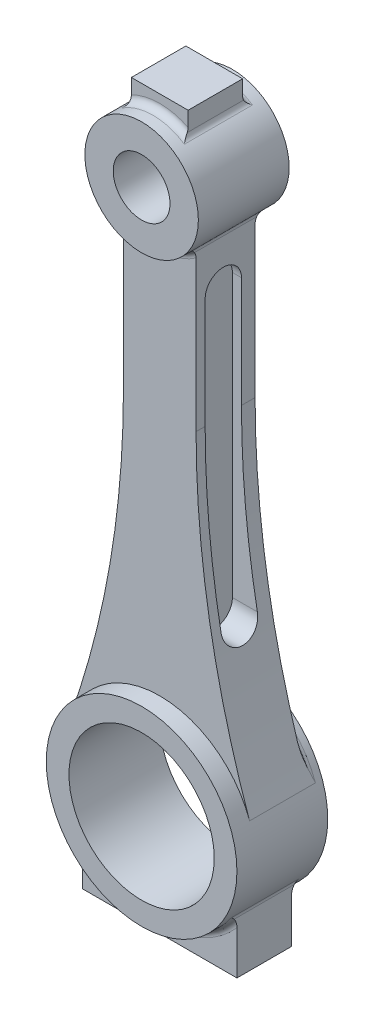
SolidWorks part; units mm, degrees
ref_plane "Front Plane" through (0, 0, 0) normal (0, 0, 1) x (1, 0, 0)
ref_plane "Top Plane" through (0, 0, 0) normal (0, 1, 0) x (1, 0, 0)
ref_plane "Right Plane" through (0, 0, 0) normal (1, 0, 0) x (0, 0, -1)
sketch "Sketch1" plane through (0, 0, 0) normal (0, 0, 1) x (1, 0, 0)
  circle A0 centre (0, 0) radius 21
  circle A1 centre (0, 0) radius 16
  circle A2 centre (0, 120) radius 12.5
  circle A3 centre (0, 120) radius 6.25
  dimension "D1" = 42
  dimension "D2" = 32
  dimension "D3" = 25
  dimension "D4" = 12.5
  dimension "D5" = 120
extrude "Boss-Extrude1" add sketch "Sketch1" along normal mid plane 20
sketch "Sketch2" plane through (0, 0, 10) normal (0, 0, 1) x (1, 0, 0)
  line L0 (0, 118.8569) -> (0, 91.5124) construction
  line L1 (8, 110.3953) -> (8, 75.3953)
  line L2 (-8, 110.3953) -> (-8, 75.3953)
  circle A0 centre (0, 120) radius 12.5 construction
  arc A1 (8, 75.3953) -> (19.7874, 7.0327) centre (212.1328, 75.3953) ccw
  circle A2 centre (0, 0) radius 21 construction
  arc A3 (-8, 75.3953) -> (-19.7874, 7.0327) centre (-212.1328, 75.3953) cw
  arc A4 (-19.7874, 7.0327) -> (19.7874, 7.0327) centre (0, 0) cw
  arc A6 (-8, 110.3953) -> (8, 110.3953) centre (0, 120) ccw
  dimension "D1" = 8
  dimension "D2" = 35
extrude "Boss-Extrude3" add sketch "Sketch2" against normal blind 17 and the other way blind 1
sketch "Sketch3" plane through (0, 0, 11) normal (0, 0, 1) x (1, 0, 0)
  line L2 (-8, 110.3953) -> (-8, 75.3953)
  line L3 (8, 75.3953) -> (8, 110.3953)
  line L4 (-8, 110.3953) -> (-8, 75.3953)
  line L5 (8, 75.3953) -> (8, 110.3953)
  arc A4 (-8, 110.3953) -> (8, 110.3953) centre (0, 120) ccw
  arc A5 (-19.7874, 7.0327) -> (-8, 75.3953) centre (-212.1328, 75.3953) ccw
  arc A6 (19.7874, 7.0327) -> (-19.7874, 7.0327) centre (0, 0) ccw
  arc A7 (8, 75.3953) -> (19.7874, 7.0327) centre (212.1328, 75.3953) ccw
  arc A8 (-8, 110.3953) -> (8, 110.3953) centre (0, 120) ccw
  arc A9 (-19.7874, 7.0327) -> (-8, 75.3953) centre (-212.1328, 75.3953) ccw
  arc A10 (19.7874, 7.0327) -> (-19.7874, 7.0327) centre (0, 0) ccw
  arc A11 (8, 75.3953) -> (19.7874, 7.0327) centre (212.1328, 75.3953) ccw
  dimension "D1" = 0
extrude "Cut-Extrude1" cut sketch "Sketch3" against normal blind 5
sketch "Sketch4" plane through (0, 0, 0) normal (0, 0, 1) x (1, 0, 0)
  line L0 (0, 139.5233) -> (0, -46.5002) construction
  line L1 (-6.25, 135.8253) -> (-6.25, 130.8253)
  line L2 (6.25, 135.8253) -> (6.25, 130.8253)
  line L3 (-6.25, 135.8253) -> (6.25, 135.8253)
  line L4 (-17, -24.3288) -> (-17, -12.3288)
  line L5 (17, -24.3288) -> (17, -12.3288)
  line L6 (-17, -24.3288) -> (17, -24.3288)
  circle A0 centre (0, 120) radius 12.5 construction
  circle A1 centre (0, 120) radius 12.5
  circle A2 centre (0, 0) radius 21 construction
  circle A3 centre (0, 0) radius 21
  dimension "D1" = 5
  dimension "D2" = 12.5
  dimension "D3" = 12
  dimension "D4" = 34
extrude "Boss-Extrude4" add sketch "Sketch4" along normal mid plane 12 contours L0 A3 L4 L6 | A3 L0 L6 L5 | L0 L3 L1 A1 | L3 L0 A1 L2
fillet "Fillet1" radius 1.5 4 edges at (0, 132.5, 6) (-6.25, 130.8253, 0) (6.25, 130.8253, 0) (0, 132.5, -6)
fillet "Fillet2" radius 1.5 4 edges at (0, 107.5, -7) (-8, 110.3953, -0.5) (8, 110.3953, -0.5) (0, 107.5, 6)
fillet "Fillet3" radius 1.5 1 edges at (0, 21, -7)
fillet "Fillet4" radius 1.5 4 edges at (0, -21, 6) (17, -12.3288, 0) (-17, -12.3288, 0) (0, -21, -6)
ref_plane "Plane1" through (6, 0, 0) normal (1, 0, 0) x (0, 0, -1)
sketch "Sketch5" plane through (6, 0, 0) normal (1, 0, 0) x (0, 0, -1)
  line L0 (0, 99.7538) -> (0, 37.7538) construction
  line L1 (4, 99.7538) -> (4, 37.7538)
  line L2 (-4, 99.7538) -> (-4, 37.7538)
  line L3 (-26.0399, 119.7538) -> (33.3357, 119.7538) construction
  arc A0 (4, 99.7538) -> (-4, 99.7538) centre (0, 99.7538) ccw
  arc A1 (-4, 37.7538) -> (4, 37.7538) centre (0, 37.7538) ccw
  point P3 (0, 68.7538)
  dimension "D1" = 4
  dimension "D2" = 62
  dimension "D3" = 20
extrude "Cut-Extrude2" cut sketch "Sketch5" along normal through all
mirror "Mirror1" about plane through (0, 0, 0) normal (1, 0, 0) of "Cut-Extrude2"
